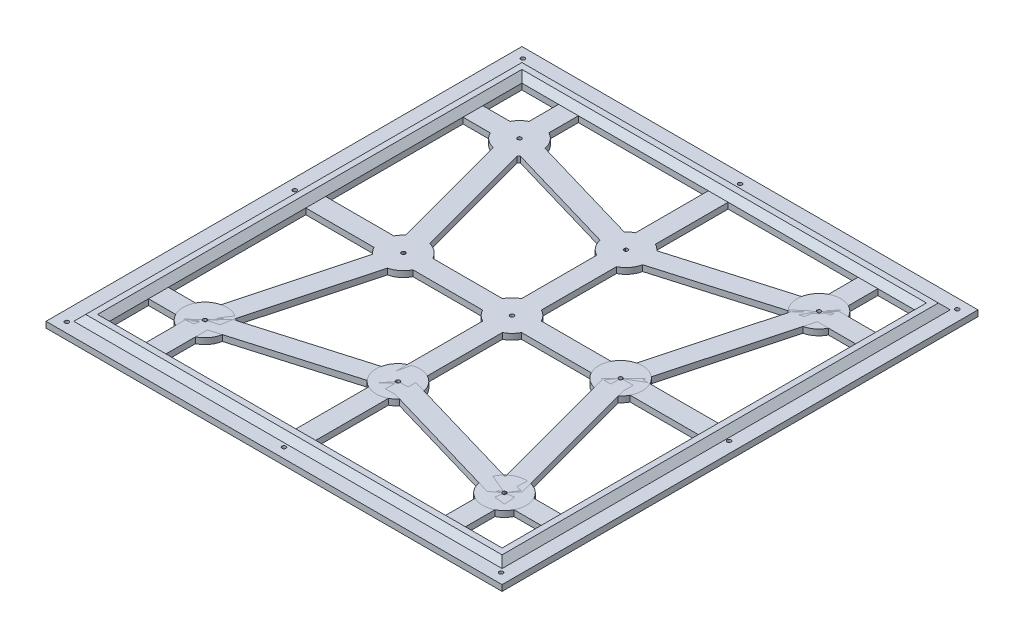
SolidWorks part; units mm, degrees
ref_plane "Front Plane" through (0, 0, 0) normal (0, 0, 1) x (1, 0, 0)
ref_plane "Top Plane" through (0, 0, 0) normal (0, 1, 0) x (1, 0, 0)
ref_plane "Right Plane" through (0, 0, 0) normal (1, 0, 0) x (0, 0, -1)
sketch "Sketch1" plane through (0, 0, 0) normal (0, 1, 0) x (1, 0, 0)
  line L1 (-115, 120) -> (115, 120)
  line L2 (-115, 120) -> (-115, -120)
  line L3 (-115, -120) -> (115, -120)
  line L4 (115, 120) -> (115, -120)
  line L5 (-115, 120) -> (115, -120) construction
  line L6 (-115, -120) -> (115, 120) construction
  point P0 (0, 0)
  dimension "D1" = 240
  dimension "D2" = 230
extrude "Boss-Extrude1" add sketch "Sketch1" along normal blind 3
sketch "Sketch2" plane through (0, 3, 0) normal (0, 1, 0) x (1, 0, 0)
  line L0 (0, -115) -> (0, 0) construction
  line L5 (-109.5, 115) -> (109.5, 115) construction
  line L7 (-109.5, 115) -> (-109.5, -115) construction
  line L8 (-109.5, -115) -> (109.5, -115) construction
  line L9 (115, -120) -> (115, 120)
  line L11 (115, 120) -> (-115, 120)
  line L13 (-115, 120) -> (-115, -120)
  line L15 (-115, -120) -> (115, -120)
  line L16 (115, -120) -> (115, 120) construction
  line L17 (115, 120) -> (-115, 120) construction
  line L18 (-115, 120) -> (-115, -120) construction
  line L19 (-115, -120) -> (115, -120) construction
  line L20 (109.5, 115) -> (109.5, -115) construction
  line L21 (-109.5, 115) -> (109.5, -115) construction
  line L22 (-109.5, -115) -> (109.5, 115) construction
  line L23 (-109.5, 0) -> (0, 0) construction
  line L24 (0, 0) -> (109.5, 0) construction
  line L25 (0, 0) -> (0, 115) construction
  circle A0 centre (0, 0) radius 109.5 construction
  circle A1 centre (-109.5, -115) radius 1
  circle A2 centre (109.5, -115) radius 1
  circle A3 centre (0, -115) radius 1
  circle A4 centre (-75.5086, -79.3013) radius 1
  circle A5 centre (75.5086, -79.3013) radius 1
  circle A6 centre (0, 0) radius 1
  circle A7 centre (-109.5, 0) radius 1
  circle A8 centre (-109.5, 115) radius 1
  circle A9 centre (-75.5086, 79.3013) radius 1
  circle A10 centre (75.5086, 79.3013) radius 1
  circle A11 centre (0, 115) radius 1
  circle A12 centre (109.5, 115) radius 1
  circle A13 centre (109.5, 0) radius 1
  circle A14 centre (0, 57.5) radius 1
  circle A15 centre (0, -57.5) radius 1
  circle A16 centre (-54.75, 0) radius 1
  circle A17 centre (54.75, 0) radius 1
  point P2 (0, 0)
  dimension "D1" = 0
  dimension "D2" = 219
  dimension "D3" = 5
  dimension "D4" = 2
  dimension "D5" = 240
extrude "Cut-Extrude1" cut sketch "Sketch2" against normal up to next
sketch "Sketch4" plane through (0, 3, 0) normal (0, 1, 0) x (1, 0, 0)
  line L12 (115, -120) -> (115, 120)
  line L13 (115, 120) -> (-115, 120)
  line L14 (-115, 120) -> (-115, -120)
  line L15 (-115, -120) -> (115, -120)
  line L16 (115, -120) -> (115, 120) construction
  line L17 (115, 120) -> (-115, 120) construction
  line L18 (-115, 120) -> (-115, -120) construction
  line L19 (-115, -120) -> (115, -120) construction
  line L24 (105, -110) -> (105, 110)
  line L25 (105, 110) -> (-105, 110)
  line L26 (-105, 110) -> (-105, -110)
  line L27 (-105, -110) -> (105, -110)
  line L28 (105, -110) -> (105, 110)
  line L29 (105, 110) -> (-105, 110)
  line L30 (-105, 110) -> (-105, -110)
  line L31 (-105, -110) -> (105, -110)
  line L36 (102, -107) -> (102, 107)
  line L37 (102, 107) -> (-102, 107)
  line L38 (-102, 107) -> (-102, -107)
  line L39 (-102, -107) -> (102, -107)
  line L40 (102, -107) -> (102, 107)
  line L41 (102, 107) -> (-102, 107)
  line L42 (-102, 107) -> (-102, -107)
  line L43 (-102, -107) -> (102, -107)
  dimension "D1" = 0
  dimension "D2" = 10
  dimension "D3" = 13
extrude "Boss-Extrude2" add sketch "Sketch4" along normal blind 3
chamfer "Chamfer1" distance 3 angle 45 8 edges at (0, 3, -110) (105, 3, 0) (0, 3, 110) (-105, 3, 0) (0, 3, -107) (102, 3, 0) (0, 3, 107) (-102, 3, 0)
sketch "Sketch5" plane through (0, 3, 0) normal (0, 1, 0) x (1, 0, 0)
  line L8 (99, -104) -> (99, 104)
  line L9 (99, 104) -> (-99, 104)
  line L10 (-99, 104) -> (-99, -104)
  line L11 (-99, -104) -> (99, -104)
  line L12 (99, -104) -> (99, 104)
  line L13 (99, 104) -> (-99, 104)
  line L14 (-99, 104) -> (-99, -104)
  line L15 (-99, -104) -> (99, -104)
  circle A0 centre (0, 0) radius 1 construction
  circle A1 centre (0, 0) radius 1 construction
  circle A2 centre (0, 0) radius 11
  circle A4 centre (75.5086, 79.3013) radius 11
  circle A5 centre (54.75, 0) radius 11
  circle A6 centre (-54.75, 0) radius 11
  circle A7 centre (0, -57.5) radius 11
  circle A8 centre (0, 57.5) radius 11
  circle A9 centre (-75.5086, 79.3013) radius 11
  circle A10 centre (75.5086, -79.3013) radius 11
  circle A11 centre (-75.5086, -79.3013) radius 11
  circle A26 centre (75.5086, 79.3013) radius 1
  circle A27 centre (75.5086, 79.3013) radius 1 construction
  circle A28 centre (54.75, 0) radius 1
  circle A29 centre (54.75, 0) radius 1 construction
  circle A30 centre (-54.75, 0) radius 1
  circle A31 centre (-54.75, 0) radius 1 construction
  circle A32 centre (0, -57.5) radius 1
  circle A33 centre (0, -57.5) radius 1 construction
  circle A34 centre (0, 57.5) radius 1
  circle A35 centre (0, 57.5) radius 1 construction
  circle A36 centre (-75.5086, 79.3013) radius 1
  circle A37 centre (-75.5086, 79.3013) radius 1 construction
  circle A38 centre (75.5086, -79.3013) radius 1
  circle A39 centre (75.5086, -79.3013) radius 1 construction
  circle A40 centre (-75.5086, -79.3013) radius 1
  circle A41 centre (-75.5086, -79.3013) radius 1 construction
  dimension "D5" = 0
  dimension "D1" = 0
  dimension "D3" = 0
  dimension "D2" = 0
  dimension "D4" = 0
  dimension "D6" = 0
  dimension "D7" = 0
  dimension "D8" = 0
  dimension "D9" = 10
  dimension "D10" = 0
extrude "Cut-Extrude2" cut sketch "Sketch5" against normal up to next
sketch "Sketch6" plane through (0, 3, 0) normal (0, 1, 0) x (1, 0, 0)
  line L0 (-55.75, 0) -> (-99, 0)
  line L1 (-99, 104) -> (-99, -104) construction
  line L2 (-74.5489, 79.0205) -> (-1, 57.5)
  line L3 (-75.5086, 78.3013) -> (-54.75, 1)
  line L4 (1, 57.5) -> (-1, 57.5) construction
  line L5 (0, 56.5) -> (0, 1)
  line L6 (75.5086, 79.3013) -> (75.5086, 78.3013) construction
  line L7 (54.75, 1) -> (54.75, -1) construction
  line L8 (-76.5086, 79.3013) -> (-99, 79.3013)
  line L9 (-75.5086, 80.3013) -> (-75.5086, 104)
  line L10 (99, 104) -> (-99, 104) construction
  line L11 (53.75, 0) -> (1, 0)
  line L12 (-54.75, 1) -> (-54.75, -1) construction
  line L13 (-75.5086, 79.3013) -> (-75.5086, 78.3013) construction
  line L14 (75.5086, 80.3013) -> (75.5086, 104)
  line L15 (76.5086, 79.3013) -> (99, 79.3013)
  line L16 (75.5086, 78.3013) -> (54.75, 1)
  line L17 (74.5489, 79.0205) -> (1, 57.5)
  line L18 (0, 58.5) -> (0, 104)
  line L19 (55.75, 0) -> (99, 0)
  line L20 (-53.75, 0) -> (-1, 0)
  line L21 (-75.5086, -79.3013) -> (-75.5086, -78.3013) construction
  line L22 (75.5086, -79.3013) -> (75.5086, -78.3013) construction
  line L23 (1, -57.5) -> (-1, -57.5) construction
  line L24 (0, -58.5) -> (0, -104)
  line L25 (74.5489, -79.0205) -> (1, -57.5)
  line L26 (75.5086, -78.3013) -> (54.75, -1)
  line L27 (76.5086, -79.3013) -> (99, -79.3013)
  line L28 (75.5086, -80.3013) -> (75.5086, -104)
  line L29 (-75.5086, -80.3013) -> (-75.5086, -104)
  line L30 (-76.5086, -79.3013) -> (-99, -79.3013)
  line L31 (0, -56.5) -> (0, -1)
  line L32 (-75.5086, -78.3013) -> (-54.75, -1)
  line L33 (-74.5489, -79.0205) -> (-1, -57.5)
  circle A6 centre (-75.5086, 79.3013) radius 1 construction
  circle A7 centre (0, 57.5) radius 1 construction
  circle A9 centre (-54.75, 0) radius 1 construction
  circle A10 centre (0, 0) radius 1 construction
  point P12 (0, 57.5)
  point P40 (-54.75, 0)
  point P41 (54.75, 0)
  point P69 (0, -57.5)
extrude "Extrude-Thin2" add sketch "Sketch6" against normal up to surface (3 mm away) thin up to face at (75.5086, 0, -78.3013) thin type mid plane wall 10
